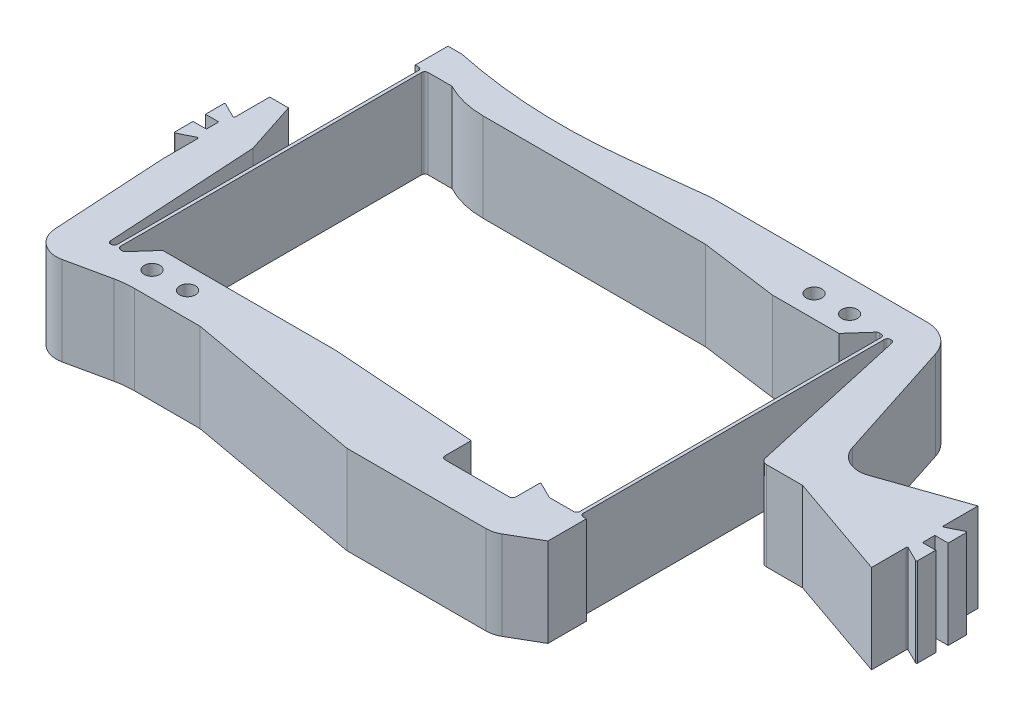
SolidWorks part; units mm, degrees
material "6061-O (SS)"
ref_plane "Front Plane" through (0, 0, 0) normal (0, 0, 1) x (1, 0, 0)
ref_plane "Top Plane" through (0, 0, 0) normal (0, 1, 0) x (1, 0, 0)
ref_plane "Right Plane" through (0, 0, 0) normal (1, 0, 0) x (0, 0, -1)
sketch "Sketch1" plane through (0, 0, 0) normal (0, 1, 0) x (1, 0, 0)
  line L1 (-76.2, 0) -> (76.2, 0) construction
  line L7 (0, 43.9941) -> (-76.2, 0) construction
  line L8 (76.2, 0) -> (0, 43.9941) construction
  line L9 (-43.0927, 22) -> (-43.0927, -22) construction
  line L10 (9.8199, -19.0502) -> (-29.8041, -19.0502)
  line L11 (9.8199, -19.0502) -> (9.8199, 19.0502)
  line L12 (9.8199, 19.0502) -> (-29.8041, 19.0502)
  line L13 (-29.8041, -19.0502) -> (-29.8041, 19.0502)
  line L14 (9.8199, -19.0502) -> (-29.8041, 19.0502) construction
  line L15 (9.8199, 19.0502) -> (-29.8041, -19.0502) construction
  line L16 (-29.8041, 19.0502) -> (-39.3291, 19.0502)
  line L17 (-29.8041, 19.0502) -> (-29.8041, -19.0502)
  line L18 (-29.8041, -19.0502) -> (-39.3291, -19.0502)
  line L19 (-39.3291, 19.0502) -> (-39.3291, -19.0502)
  line L20 (9.8199, -19.0502) -> (19.3449, -19.0502)
  line L21 (9.8199, -19.0502) -> (9.8199, 19.0502)
  line L22 (9.8199, 19.0502) -> (19.3449, 19.0502)
  line L23 (19.3449, -19.0502) -> (19.3449, 19.0502)
  line L24 (23.1085, 22) -> (23.1085, -22) construction
  line L25 (-43.3213, 22) -> (-43.3213, -22)
  line L26 (22.8799, 22) -> (22.8799, -22)
  line L27 (-42.8641, 22) -> (-42.8641, -22)
  line L28 (23.3371, 22) -> (23.3371, -22)
  line L29 (-42.8641, -5.4114) -> (-39.3291, -5.4114) construction
  line L30 (22.8799, -5.4114) -> (19.3449, -5.4114) construction
  line L31 (0, 0) -> (0, 43.9941) construction
  line L32 (-52.8845, 13.4612) -> (-51.8236, 31.3444) construction
  line L33 (-51.8236, 31.3444) -> (-30.0207, 26.6616) construction
  line L34 (-45.0888, 7.62) -> (-45.0888, -7.62) construction
  line L35 (-44.2357, 22) -> (-43.3213, 22)
  line L36 (-50.6866, 7.62) -> (-49.4633, 28.2396)
  line L37 (-49.4633, 28.2396) -> (-19.3998, 21.7826)
  line L38 (-49.4633, 28.2396) -> (-30.5541, 24.1783) construction
  line L39 (52.8845, 13.4612) -> (36.8667, 5.4384) construction
  line L40 (36.8667, 5.4384) -> (30.0207, 26.6616) construction
  line L41 (0, 43.9941) -> (-30.0207, 26.6616) construction
  line L42 (53.8514, 11.5308) -> (35.5843, 2.3813)
  line L43 (35.5843, 2.3813) -> (27.9659, 25.9988)
  line L44 (24.2515, 22) -> (28.7842, 23.4621) construction
  line L45 (35.5843, 2.3813) -> (35.5843, -2.3813) construction
  line L46 (-44.2357, 22) -> (-45.0888, 7.62)
  line L47 (-45.0888, -7.62) -> (-44.2357, -22)
  line L48 (-50.349, 13.3108) -> (-49.4633, 28.2396) construction
  line L49 (53.8514, -11.5308) -> (35.5843, -2.3813)
  line L50 (-43.3213, -22) -> (-44.2357, -22)
  line L52 (35.5843, -2.3813) -> (27.9659, -25.9988)
  line L53 (-49.4633, -28.2396) -> (-19.3998, -21.7826)
  line L54 (-50.6866, -7.62) -> (-49.4633, -28.2396)
  line L55 (23.3371, 22) -> (24.2515, 22)
  line L56 (76.2, 0) -> (0, -43.9941) construction
  line L57 (0, -43.9941) -> (-76.2, 0) construction
  line L58 (71.882, 0) -> (0, -41.5011)
  line L59 (0, -41.5011) -> (-71.882, 0)
  line L60 (0, 41.5011) -> (-71.882, 0)
  line L61 (71.882, 0) -> (0, 41.5011)
  line L62 (27.5523, -28.2396) -> (-2.5112, -21.7826)
  line L63 (27.5523, 28.2396) -> (-2.5112, 21.7826)
  circle A0 centre (-43.0927, 22) radius 4.7627 construction
  circle A3 centre (24.2515, 22) radius 4.7627 construction
  point P2 (0, 0)
  point P12 (-9.9921, 0)
  point P46 (35.5843, 0)
  point P47 (0, 43.9941)
  point P57 (0, 43.9941)
  point P64 (-45.0888, 0)
  point P70 (-43.3213, 0)
  point P77 (-10.9555, 0)
  dimension "D4" = 38.1004
  dimension "D5" = 39.624
  dimension "D6" = 9.525
  dimension "D7" = 44
  dimension "D8" = 150
  dimension "D13" = 1.7675
  dimension "D2" = 152.4
  dimension "D19" = 0.9144
  dimension "D14" = 5.588
  dimension "D15" = 15.24
  dimension "D3" = 4.7627
  dimension "D11" = 3.535
  dimension "D9" = 0.2286
  dimension "D18" = 2.159
  dimension "D17" = 2.159
  dimension "D16" = 2
  dimension "D20" = 2
sketch "Sketch2" plane through (0, 0, 0) normal (0, 1, 0) x (1, 0, 0)
  line L3 (-29.8041, -19.0502) -> (-29.8041, 19.0502) construction
  line L7 (9.8199, 19.0502) -> (19.3449, 19.0502)
  line L10 (-50.6806, 7.62) -> (-47.9942, 7.62)
  line L11 (-47.9942, 7.62) -> (-45.5383, 0.0647)
  line L12 (-45.5383, 0.0647) -> (-44.2357, -22)
  line L13 (-44.2357, -22) -> (-41.9497, -22)
  line L14 (-41.9497, -22) -> (-39.3291, -19.0502)
  line L24 (-30.1531, 24.0922) -> (-6.6386, 26.7627)
  line L25 (-39.3291, -19.0502) -> (-14.5241, -19.0502)
  line L26 (9.8199, -19.0502) -> (-29.8041, -19.0502) construction
  line L29 (9.8199, 19.0502) -> (-1.2291, 20.5502)
  line L30 (9.8199, 19.0502) -> (-29.8041, 19.0502) construction
  line L32 (16.4949, -22) -> (29.7221, -22) construction
  line L34 (71.882, 0) -> (0, -41.5011) construction
  line L36 (0, -41.5011) -> (-71.882, 0) construction
  line L37 (-34.5666, -6.7134) -> (-34.5666, -25.7742) construction
  line L38 (-37.9845, -25.7742) -> (-49.4633, -28.2396)
  line L39 (-49.4633, -28.2396) -> (-50.6806, -7.62)
  line L40 (-50.6806, -7.62) -> (-50.6806, 7.62)
  line L43 (-49.4633, 28.2396) -> (-19.3998, 21.7826) construction
  line L44 (-42.2453, 26.6893) -> (-30.1531, 24.0922)
  line L45 (0, 41.5011) -> (-71.882, 0) construction
  line L47 (28.7842, 23.4621) -> (35.5843, 2.3813)
  line L48 (35.5843, 2.3813) -> (50.6806, 7.62)
  line L49 (-6.6386, 26.7627) -> (24.2515, 26.7627)
  line L51 (-39.3291, -6.7134) -> (-29.8041, -6.7134) construction
  line L52 (50.6806, -7.62) -> (35.5843, -2.3813)
  line L53 (35.5843, -2.3813) -> (29.6871, -2.3813)
  line L54 (29.6871, -2.3813) -> (24.2515, 22)
  line L55 (24.2515, 22) -> (21.9655, 22)
  line L61 (19.2496, -30.3873) -> (-1.6246, -30.3873)
  line L64 (-1.2291, 20.5502) -> (-36.4963, 20.5502)
  line L68 (-42.2453, 26.6893) -> (-48.2113, 26.6893)
  line L69 (-1.6246, -30.3873) -> (-27.2398, -25.7742)
  line L70 (-38.9574, 22) -> (-36.4963, 20.5502)
  line L71 (16.4949, -22) -> (16.4949, -24.7993)
  line L73 (21.9655, 22) -> (19.3449, 19.0502)
  line L74 (16.4949, -24.7993) -> (6.3199, -24.7993)
  line L75 (6.3199, -24.7993) -> (6.3199, -20.5502)
  line L76 (6.3199, -20.5502) -> (-14.5241, -19.0502)
  line L77 (19.2496, -30.3873) -> (29.7221, -24.341)
  line L78 (9.8199, -19.0502) -> (12.9949, -19.0502) construction
  line L79 (9.8199, -19.0502) -> (9.8199, -23.7833) construction
  line L80 (9.8199, -23.7833) -> (12.9949, -23.7833) construction
  line L81 (12.9949, -19.0502) -> (12.9949, -23.7833) construction
  line L82 (29.7221, -24.341) -> (29.7221, -22)
  line L83 (0, 0) -> (0, 13.8808) construction
  line L84 (50.6806, -7.62) -> (50.6806, 7.62)
  line L85 (-37.9845, -25.7742) -> (-27.2398, -25.7742)
  line L86 (-39.3291, 19.0502) -> (-39.3291, -19.0502) construction
  line L87 (-49.4633, -28.2396) -> (-19.3998, -21.7826) construction
  line L90 (9.8199, 19.0502) -> (-29.8041, -19.0502) construction
  line L91 (-38.9574, 22) -> (-48.2113, 22)
  line L92 (-48.2113, 26.6893) -> (-48.2113, 22)
  line L95 (-76.2, 0) -> (76.2, 0) construction
  line L96 (16.4949, -22) -> (16.4949, -20.7842)
  line L97 (23.3371, 22) -> (23.3371, -22) construction
  line L99 (16.4949, -20.7842) -> (18.9624, -22)
  line L100 (29.7221, -22) -> (18.9624, -22)
  circle A0 centre (24.2515, 22) radius 4.7627 construction
  arc A1 (24.2515, 26.7627) -> (28.7842, 23.4621) centre (24.2515, 22) cw
  circle A2 centre (-41.9497, -22) radius 4.5227 construction
  circle A3 centre (-44.2357, -22) radius 5.5863 construction
  point P10 (23.1085, 22)
  point P19 (50.6806, 0)
  point P44 (-43.0927, -22)
  point P50 (23.1085, -22)
  point P51 (-9.9921, 0)
  point P112 (-9.9514, 0)
  dimension "D2" = 9.0453
  dimension "D4" = 11.1726
  dimension "D1" = 28.575
  dimension "D5" = 3.5
  dimension "D6" = 3.5
  dimension "D7" = 3.175
  dimension "D8" = 5.588
  dimension "D9" = 1.016
  dimension "D10" = 1.5
  dimension "D3" = 9.525
  dimension "D11" = 9.525
  dimension "D13" = 57.15
  dimension "D12" = 1.5
  dimension "D15" = 25.5194
  dimension "D14" = 2.4675
  dimension "D16" = 6.35
extrude "Boss-Extrude1" add sketch "Sketch2" along normal blind 6.35 and the other way blind 6.35
sketch "Sketch3" plane through (0, 0, 0) normal (0, 1, 0) x (1, 0, 0)
  line L0 (-42.8641, 22) -> (-42.8641, -22) construction
  line L1 (-42.8641, 22.508) -> (-43.3213, 22.508)
  line L2 (-42.8641, 22.508) -> (-42.8641, -22)
  line L3 (-42.8641, -22) -> (-43.3213, -22)
  line L4 (-43.3213, 22.508) -> (-43.3213, -22)
  line L5 (22.8799, -22) -> (23.3371, -22)
  line L6 (22.8799, -22) -> (22.8799, 22.508)
  line L7 (22.8799, 22.508) -> (23.3371, 22.508)
  line L8 (23.3371, -22) -> (23.3371, 22.508)
  line L9 (23.3371, 22) -> (23.3371, -22) construction
  line L10 (-48.2113, 22) -> (-38.9574, 22) construction
  dimension "D1" = 0.508
extrude "Boss-Extrude2" add sketch "Sketch3" along normal through all and the other way through all
sketch "Sketch7" plane through (0, 0, 0) normal (0, 1, 0) x (1, 0, 0)
  line L0 (-50.6806, 0) -> (-50.6806, 2.54) construction
  line L1 (-50.6806, 7.62) -> (-50.6806, -7.62) construction
  line L2 (-50.6806, 2.54) -> (-53.2206, 3.81) construction
  line L3 (-53.2206, 3.81) -> (-53.2206, -3.81) construction
  line L4 (-53.2206, -3.81) -> (-50.6806, -2.54) construction
  line L5 (-50.6806, -2.54) -> (-50.6806, 0) construction
  line L6 (0, 0) -> (0, 12.9706) construction
  line L7 (-76.2, 0) -> (76.2, 0) construction
  line L8 (0, 0) -> (0, 43.9941) construction
  line L14 (-53.1444, 3.6867) -> (-53.1444, -3.6867)
  line L15 (-53.1444, -3.6867) -> (-50.7568, -2.4929)
  line L16 (-50.7568, -2.4929) -> (-50.7568, 0) construction
  line L17 (-50.7568, 0) -> (-50.7568, 2.4929) construction
  line L18 (-50.7568, 2.4929) -> (-53.1444, 3.6867)
  line L19 (-50.7568, 2.4929) -> (-50.6806, 2.4548)
  line L20 (-50.6806, 2.4548) -> (-50.6806, -2.4548)
  line L21 (-50.6806, -2.4548) -> (-50.7568, -2.4929)
  line L22 (50.6806, 2.4548) -> (50.6806, -2.4548)
  line L23 (50.7568, 2.4929) -> (50.6806, 2.4548)
  line L24 (50.7568, 2.4929) -> (53.1444, 3.6867)
  line L25 (53.1444, 3.6867) -> (53.1444, -3.6867)
  line L26 (53.1444, -3.6867) -> (50.7568, -2.4929)
  line L27 (50.6806, -2.4548) -> (50.7568, -2.4929)
  dimension "D1" = 2.54
  dimension "D2" = 7.62
  dimension "D3" = 2.54
  dimension "D4" = 0.0762
extrude "Boss-Extrude4" add sketch "Sketch7" along normal through all and the other way through all
sketch "Sketch8" plane through (0, 6.35, 0) normal (0, 1, 0) x (1, 0, 0)
  line L0 (-76.2, 0) -> (76.2, 0) construction
  line L1 (-51.2394, -0.889) -> (-53.2714, -0.889)
  line L2 (-51.2394, -0.889) -> (-51.2394, 0.889)
  line L3 (-51.2394, 0.889) -> (-53.2714, 0.889)
  line L4 (-53.2714, -0.889) -> (-53.2714, 0.889)
  line L5 (-51.2394, -0.889) -> (-53.2714, 0.889) construction
  line L6 (-51.2394, 0.889) -> (-53.2714, -0.889) construction
  line L7 (-53.1444, 3.6867) -> (-53.1444, -3.6867) construction
  line L8 (0, 0) -> (0, 15.7634) construction
  line L9 (0, 0) -> (0, 43.9941) construction
  line L10 (51.2394, 0.889) -> (53.2714, -0.889) construction
  line L11 (51.2394, -0.889) -> (53.2714, 0.889) construction
  line L12 (53.2714, -0.889) -> (53.2714, 0.889)
  line L13 (51.2394, 0.889) -> (53.2714, 0.889)
  line L14 (51.2394, -0.889) -> (51.2394, 0.889)
  line L15 (51.2394, -0.889) -> (53.2714, -0.889)
  point P0 (-52.2554, 0)
  point P18 (52.2554, 0)
  dimension "D1" = 2.032
  dimension "D2" = 1.778
  dimension "D3" = 0.127
extrude "Cut-Extrude1" cut sketch "Sketch8" against normal through all
fillet "Fillet1" radius 0.4572 12 edges at (24.2515, 0, -22) (21.9655, 0, -22) (-41.9497, 0, 22) (-42.8641, 0, 22) (-44.2357, 0, 22) (-43.3213, 0, 22) (23.3371, 0, -22) (22.8799, 0, -22) (-42.8641, 0, -22) (-43.3213, 0, -22) (23.3371, 0, 22) (22.8799, 0, 22)
fillet "Fillet2" radius 0.9144 5 edges at (29.6871, 0, 2.3813) (29.7221, 0, 22) (29.7221, 0, 24.341) (-48.2113, 0, -26.6893) (-48.2113, 0, -22)
fillet "Fillet3" radius 3.556 3 edges at (35.5843, 0, -2.3813) (-49.4633, 0, 28.2396) (19.2496, 0, 30.3873)
fillet "Fillet6" radius 12.7 2 edges at (-36.4963, 0, -20.5502) (-37.9845, 0, 25.7742)
ref_axis "Axis2" through (0, 0, -43.9941) along (0, 1, 0)
pattern_circular "CirPattern3" [suppressed] count 3 over 360 about axis through (0, 0, -43.9941) along (0, 1, 0) of bodies 145 106
ref_axis "Axis3" through (-76.2, 0, 0) along (0, 1, 0)
pattern_circular "CirPattern4" [suppressed] count 3 over 360 about axis through (-76.2, 0, 0) along (0, 1, 0) of bodies 111 145 112 106
ref_plane "Plane1" [suppressed] through (-76.2, 0, 0) normal (1, 0, 0) x (0, 0, -1)
mirror "Mirror3" [suppressed] about plane through (0, 0, 0) normal (0, 0, 1) of bodies 113 111
ref_plane "Plane2" [suppressed] through (0, 0, 131.9823) normal (0, 0, 1) x (1, 0, 0)
mirror "Mirror4" [suppressed] about plane through (0, 0, 131.9823) normal (0, 0, 1) of bodies 113 115 112 111 117 145 131 116 118 132 106
sketch "Sketch9" plane through (0, 6.35, 0) normal (0, 1, 0) x (1, 0, 0)
  line L0 (-37.6781, -22.2252) -> (-32.5981, -22.2252) construction
  line L1 (12.6139, 22.2252) -> (17.6939, 22.2252) construction
  line L2 (9.8199, 19.0502) -> (19.3449, 19.0502) construction
  line L3 (9.8199, -19.0502) -> (9.8199, 19.0502) construction
  line L4 (-29.8041, -19.0502) -> (-29.8041, 19.0502) construction
  line L5 (-29.8041, -19.0502) -> (-39.3291, -19.0502) construction
  circle A0 centre (-37.6781, -22.2252) radius 1.1303
  circle A1 centre (-32.5981, -22.2252) radius 1.1303
  circle A2 centre (12.6139, 22.2252) radius 1.1303
  circle A3 centre (17.6939, 22.2252) radius 1.1303
  dimension "D3" = 2.2606
  dimension "D1" = 3.175
  dimension "D2" = 5.08
  dimension "D4" = 2.794
  dimension "D5" = 2.794
  dimension "D6" = 3.175
extrude "Cut-Extrude2" cut sketch "Sketch9" against normal through all
fillet "Fillet7" radius 0.127 1 edges at (16.4949, 0, 20.7842)
fillet "Fillet8" radius 0.508 2 edges at (6.3199, 0, 24.7993) (16.4949, 0, 24.7993)
fillet "Fillet9" radius 76.2 1 edges at (-30.1531, 0, -24.0922)
sketch "Sketch10" plane through (0, 6.35, 0) normal (0, 1, 0) x (1, 0, 0)
  line L0 (12.3091, -61.2047) -> (59.1594, 19.9424)
  line L1 (12.3091, -61.2047) -> (-59.1594, -19.9424)
  line L2 (59.1594, 19.9424) -> (-12.3091, 61.2047)
  line L3 (-59.1594, -19.9424) -> (-12.3091, 61.2047)
  line L4 (12.3091, -61.2047) -> (-12.3091, 61.2047) construction
  line L5 (59.1594, 19.9424) -> (-59.1594, -19.9424) construction
  line L6 (0, 0) -> (17.1685, 0) construction
  point P1 (0, 0)
  dimension "D1" = 93.7006
  dimension "D2" = 82.5246
  dimension "D3" = 60
sketch "Sketch11" plane through (0, 6.35, 0) normal (0, 1, 0) x (1, 0, 0)
  line L1 (47.625, 15.875) -> (-47.625, 15.875)
  line L2 (47.625, 15.875) -> (47.625, -15.875)
  line L3 (47.625, -15.875) -> (-47.625, -15.875)
  line L4 (-47.625, 15.875) -> (-47.625, -15.875)
  line L5 (47.625, 15.875) -> (-47.625, -15.875) construction
  line L6 (47.625, -15.875) -> (-47.625, 15.875) construction
  point P0 (0, 0)
  dimension "D1" = 95.25
  dimension "D2" = 31.75
sketch "Sketch12" plane through (0, 6.35, 0) normal (0, 1, 0) x (1, 0, 0)
  line L0 (-48.2113, 25.7749) -> (-48.2113, 22.9144) construction
  line L1 (-44.2357, 22) -> (-48.2113, 22)
  line L2 (-44.2357, 22) -> (-44.2357, 26.6893)
  line L3 (-44.2357, 26.6893) -> (-48.2113, 26.6893)
  line L4 (-48.2113, 22) -> (-48.2113, 26.6893)
  line L5 (-44.2357, 22) -> (-48.2113, 26.6893) construction
  line L6 (-44.2357, 26.6893) -> (-48.2113, 22) construction
  line L7 (-47.2969, 22) -> (-43.7785, 22) construction
  line L8 (-42.2453, 26.6893) -> (-47.2969, 26.6893) construction
  line L9 (-43.3213, 21.5428) -> (-43.3213, -21.5428) construction
  line L10 (28.8077, -22) -> (23.7943, -22) construction
  line L11 (29.7221, -30.3873) -> (24.2515, -30.3873)
  line L12 (29.7221, -30.3873) -> (29.7221, -22)
  line L13 (29.7221, -22) -> (24.2515, -22)
  line L14 (24.2515, -30.3873) -> (24.2515, -22)
  line L15 (29.7221, -30.3873) -> (24.2515, -22) construction
  line L16 (29.7221, -22) -> (24.2515, -30.3873) construction
  line L17 (29.7221, -23.8131) -> (29.7221, -22.9144) construction
  line L18 (23.3371, -21.5428) -> (23.3371, 21.5428) construction
  line L19 (-1.6246, -30.3873) -> (18.2968, -30.3873) construction
  point P0 (-46.2235, 24.3446)
  point P15 (26.9868, -26.1937)
  dimension "D1" = 0.9144
  dimension "D2" = 0.9144
extrude "Cut-Extrude3" cut sketch "Sketch12" against normal through all
fillet "Fillet10" radius 0.127 8 edges at (-50.6806, 0, -2.4548) (-50.6806, 0, 2.4548) (-53.1444, 0, 3.6867) (-53.1444, 0, -3.6867) (53.1444, 0, -3.6867) (50.6806, 0, -2.4548) (53.1444, 0, 3.6867) (50.6806, 0, 2.4548)
ref_plane "Plane3" through (-9.9921, 0, 0) normal (1, 0, 0) x (0, 0, -1)
equation "\"thk_mount\"= 0.375in"
equation "\"D6@Sketch1\"=\"thk_mount\""
equation "\"D9@Sketch1\"=\"D10@Sketch1\""
equation "\"tk_flex\"= 0.018in"
equation "\"D10@Sketch1\"=\"tk_flex\"/2"
equation "\"lg_link\"= 6in"
equation "\"dx\"= 3.5mm"
equation "\"D2@Sketch1\"=\"lg_link\""
equation "\"D19@Sketch1\"=\"tk_flex\"*2"
equation "\"tk_plate\"=0.5in"
equation "\"D1@Boss-Extrude1\"=\"tk_plate\"/2"
equation "\"D2@Boss-Extrude1\"=\"tk_plate\"/2"
equation "\"D5@Sketch2\"=\"dx\""
equation "\"D6@Sketch2\"=\"dx\""
equation "\"D1@Fillet2\"=\"tk_flex\"*2"
equation "\"D11@Sketch2\"=\"D3@Sketch2\""
equation "\"D12@Sketch2\"=1.5mm"
equation "\"D1@Fillet1\"=\"tk_flex\""
equation "\"D11@Sketch1\"=\"dx\"*1.01"
equation "\"D13@Sketch1\"=\"dx\"*.505"
